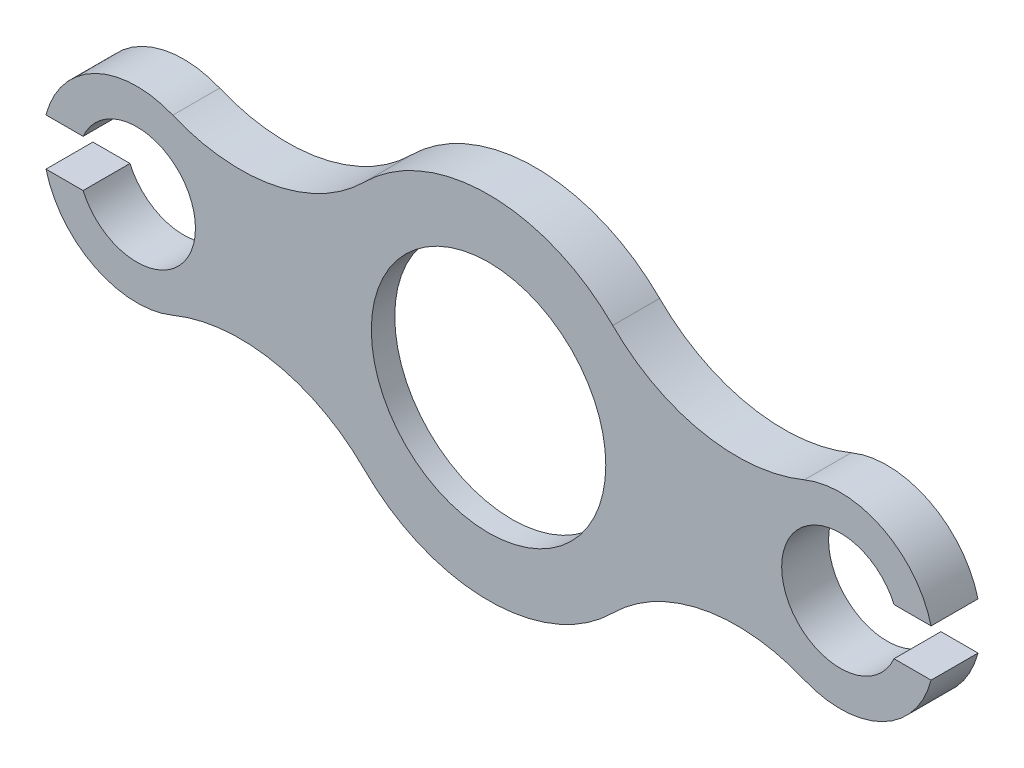
SolidWorks part; units mm, degrees
material "AISI 1020"
ref_plane "Plan de face" through (0, 0, 0) normal (0, 0, 1) x (1, 0, 0)
ref_plane "Plan de dessus" through (0, 0, 0) normal (0, 1, 0) x (1, 0, 0)
ref_plane "Plan de droite" through (0, 0, 0) normal (1, 0, 0) x (0, 0, -1)
sketch "Esquisse1" plane through (0, 0, 0) normal (0, 0, 1) x (1, 0, 0)
  line L0 (-150, 0) -> (0, 0) construction
  line L1 (0, 126.5733) -> (0, -177.595) construction
  line L2 (0, -126.5733) -> (0, 177.595) construction
  line L3 (-188.7298, -10) -> (-172.9129, -10)
  line L4 (-188.7298, 10) -> (-172.9129, 10)
  line L5 (-150, 10) -> (0, 10) construction
  line L6 (-150, -10) -> (0, -10) construction
  line L7 (188.7298, -10) -> (172.9129, -10)
  line L8 (188.7298, 10) -> (172.9129, 10)
  circle A0 centre (0, 0) radius 50
  circle A1 centre (0, 0) radius 67.8
  arc A2 (-52.9583, -53.1076) -> (52.9583, -53.1076) centre (0, 0) ccw
  arc A3 (-172.9129, -10) -> (-172.9129, 10) centre (-150, 0) ccw
  arc A4 (-188.7298, -10) -> (-134.6667, -36.9444) centre (-150, 0) ccw
  arc A7 (-134.6667, 36.9444) -> (-52.9583, 53.1076) centre (-105.9167, 106.2152) ccw
  arc A8 (-134.6667, -36.9444) -> (-52.9583, -53.1076) centre (-105.9167, -106.2152) cw
  arc A9 (134.6667, 36.9444) -> (52.9583, 53.1076) centre (105.9167, 106.2152) cw
  arc A10 (172.9129, -10) -> (172.9129, 10) centre (150, 0) cw
  arc A11 (134.6667, 36.9444) -> (188.7298, 10) centre (150, 0) cw
  arc A12 (134.6667, -36.9444) -> (52.9583, -53.1076) centre (105.9167, -106.2152) ccw
  arc A13 (-134.6667, 36.9444) -> (-188.7298, 10) centre (-150, 0) ccw
  arc A14 (52.9583, 53.1076) -> (-52.9583, 53.1076) centre (0, 0) ccw
  arc A15 (188.7298, -10) -> (134.6667, -36.9444) centre (150, 0) cw
  point P31 (-224.0379, 10)
  point P33 (-224.0379, -10)
  point P35 (0, -10)
  point P36 (0, -10)
  point P37 (0, -10)
  dimension "D1" = 100
  dimension "D2" = 135.6
  dimension "D3" = 150
  dimension "D4" = 80
  dimension "D5" = 50
  dimension "D7" = 150
  dimension "D6" = 150
  dimension "D8" = 0
  dimension "D9" = 10
  dimension "D10" = 10
extrude "Boss.-Extru.1" add sketch "Esquisse1" along normal blind 20 contours A15 L7 A10 L8 A11 A9 A14 A7 A13 L4 A3 L3 A4 A8 A2 A12 A1 | A1 A0 region at (-180.8214, -14.0617, 0) region at (-65.8823, 0, 0)
extrude "Enlèv. mat.-Extru.1" cut sketch "Esquisse1<3>" along normal blind 10 contours A1 A0 region at (-65.8823, 0, 0)
sketch "Esquisse1<3>" plane through (0, 0, 0) normal (0, 0, 1) x (1, 0, 0) same geometry as "Esquisse1"
